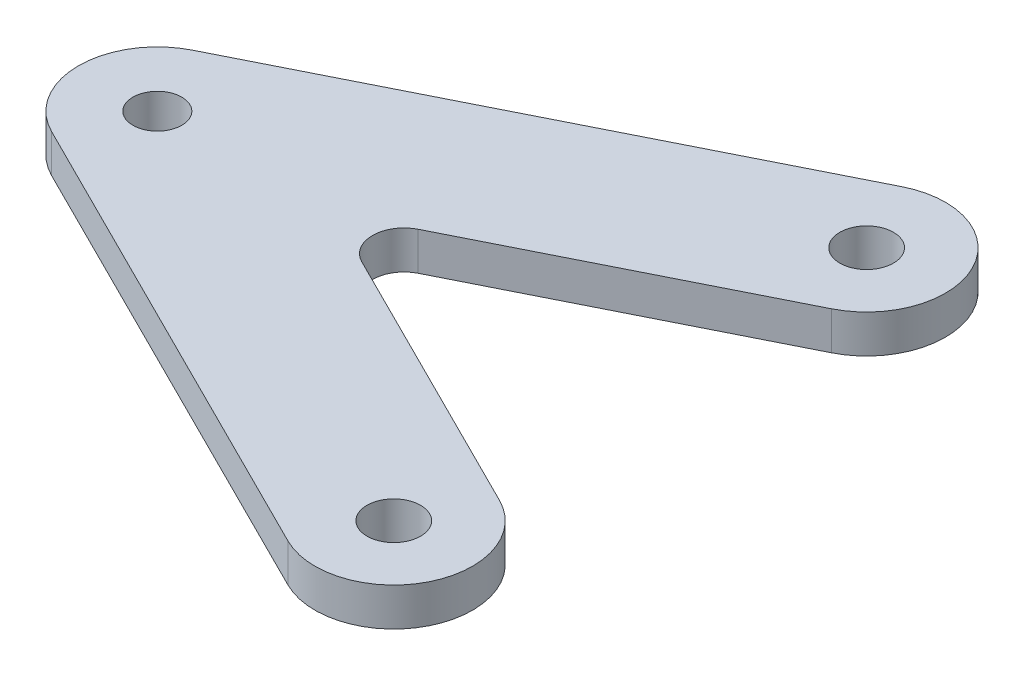
SolidWorks part; units mm, degrees
note: The reader was unsure of these and kept them because the rebuilt part matched: thickness of "Base-Flange2", "Sheet-Metal(3)", "Sheet-Metal(5)".
ref_plane "Front Plane" through (0, 0, 0) normal (0, 0, 1) x (1, 0, 0)
ref_plane "Top Plane" through (0, 0, 0) normal (0, 1, 0) x (1, 0, 0)
ref_plane "Right Plane" through (0, 0, 0) normal (1, 0, 0) x (0, 0, -1)
sketch "Sketch1" plane through (0, 0, 0) normal (0, 1, 0) x (1, 0, 0)
sketch "Sketch8" plane through (0, 0, 0) normal (0, 1, 0) x (1, 0, 0)
  line L0 (30, 15) -> (0, 0) construction
  line L1 (27.7639, 19.4721) -> (-2.2361, 4.4721)
  line L2 (-2.2361, -4.4721) -> (27.7639, -19.4721)
  line L3 (0, 0) -> (30, -15) construction
  line L4 (32.2361, 10.5279) -> (14.758, 1.7889)
  line L5 (14.758, -1.7889) -> (32.2361, -10.5279)
  line L6 (11.1803, 0) -> (0, 0) construction
  line L7 (11.1803, 0) -> (32.2361, -10.5279) construction
  line L8 (32.2361, 10.5279) -> (11.1803, 0) construction
  line L9 (-11.1803, 0) -> (27.7639, -19.4721) construction
  line L10 (27.7639, 19.4721) -> (-11.1803, 0) construction
  arc A0 (27.7639, 19.4721) -> (32.2361, 10.5279) centre (30, 15) cw
  arc A1 (27.7639, -19.4721) -> (32.2361, -10.5279) centre (30, -15) ccw
  arc A2 (14.758, -1.7889) -> (14.758, 1.7889) centre (15.6525, 0) cw
  arc A3 (-2.2361, -4.4721) -> (-2.2361, 4.4721) centre (0, 0) cw
  circle A5 centre (0, 0) radius 1.55
  dimension "D5" = 3.1
  dimension "D6" = 2
  dimension "D7" = 5
  dimension "D1" = 30
  dimension "D2" = 30
  dimension "D3" = 5
  dimension "D4" = 5
base flange "Base-Flange2" sketch "Sketch8" thickness 2.42 reverse thickness direction no parameters "D1"=0.762
hole_wizard "M3 Clearance Hole3" positions "Sketch14" profile "Sketch13" hole size "M3" standard "ANSI Metric" end condition through all
sketch "Sketch14" plane through (0, 0, 0) normal (0, 1, 0) x (1, 0, 0)
  point P0 (30, 15)
  point P3 (30, -15)
sketch "Sketch13" plane through (30, 0, -15) normal (1, 0, 0) x (0, 0, 1)
  line L0 (0, 0) -> (0, 2.42)
  line L1 (0, 2.42) -> (1.7, 2.42)
  line L2 (1.7, 2.42) -> (1.7, 0)
  line L5 (1.7, 0) -> (0, 0)
  line L11 (0, -6.35) -> (0, 107.95) construction
  dimension "Thru Hole Dia." = 3.4
  dimension "Thru Hole Depth" = 2.42
ref_point "Point1"
ref_point "Point2"
ref_plane "Plane1" through (30, 0, 0) normal (-1, 0, 0) x (0, 0, 1)
sketch "Bend-Lines1" plane through (0, 0, 0) normal (0, 1, 0) x (1, 0, 0)
sketch "Bounding-Box1" plane through (0, 0, 0) normal (0, 1, 0) x (1, 0, 0)
sheet metal parameters "Sheet-Metal(3)" thickness 2.42 parameters "D1"=0.762
flat pattern "Flat-Pattern(3)" [suppressed]
sketch "Bend-Lines3" plane through (0, 0, 0) normal (0, 1, 0) x (1, 0, 0)
sketch "Bounding-Box3" [suppressed] plane through (0, 0, 0) normal (0, 1, 0) x (1, 0, 0)
sheet metal parameters "Sheet-Metal(5)" thickness 2.42 parameters "D1"=0.762
flat pattern "Flat-Pattern(3)"
sketch "Bend-Lines3" plane through (0, 0, 0) normal (0, 1, 0) x (1, 0, 0)
sketch "Bounding-Box3" [suppressed] plane through (0, 0, 0) normal (0, 1, 0) x (1, 0, 0)
